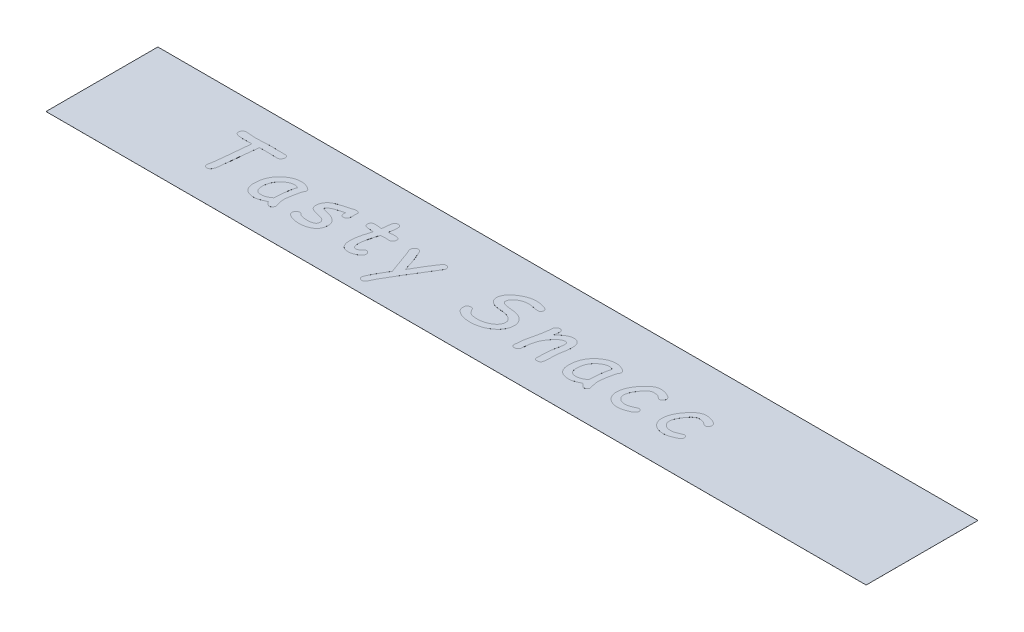
SolidWorks part; units mm, degrees
ref_plane "Front Plane" through (0, 0, 0) normal (0, 0, 1) x (1, 0, 0)
ref_plane "Top Plane" through (0, 0, 0) normal (0, 1, 0) x (1, 0, 0)
ref_plane "Right Plane" through (0, 0, 0) normal (1, 0, 0) x (0, 0, -1)
sketch "Sketch1" plane through (0, 0, 0) normal (0, 1, 0) x (1, 0, 0)
  line L1 (-48.3742, 27.9329) -> (91.3258, 27.9329)
  line L2 (-48.3742, 27.9329) -> (-48.3742, 8.8829)
  line L3 (-48.3742, 8.8829) -> (91.3258, 8.8829)
  line L4 (91.3258, 27.9329) -> (91.3258, 8.8829)
  dimension "D1" = 19.05
  dimension "D2" = 139.7
extrude "Boss-Extrude1" add sketch "Sketch1" along normal blind 0.0025
sketch "Sketch2" plane through (0, 0.0025, 0) normal (0, 1, 0) x (1, 0, 0)
  text T0 "Tasty Snacc" font "Comic Sans MS" height 8.89
  point P1 (-12.5505, 5.3495)
  point P2 (-45.8306, 11.1698)
  point P3 (0, 0)
  point P4 (0, 0)
  point P5 (0, 0)
  point P6 (-30.2954, 14.2523)
  point P7 (0, 0)
  point P8 (0, 0)
extrude "Boss-Extrude2" add sketch "Sketch2" along normal blind 0.0025
